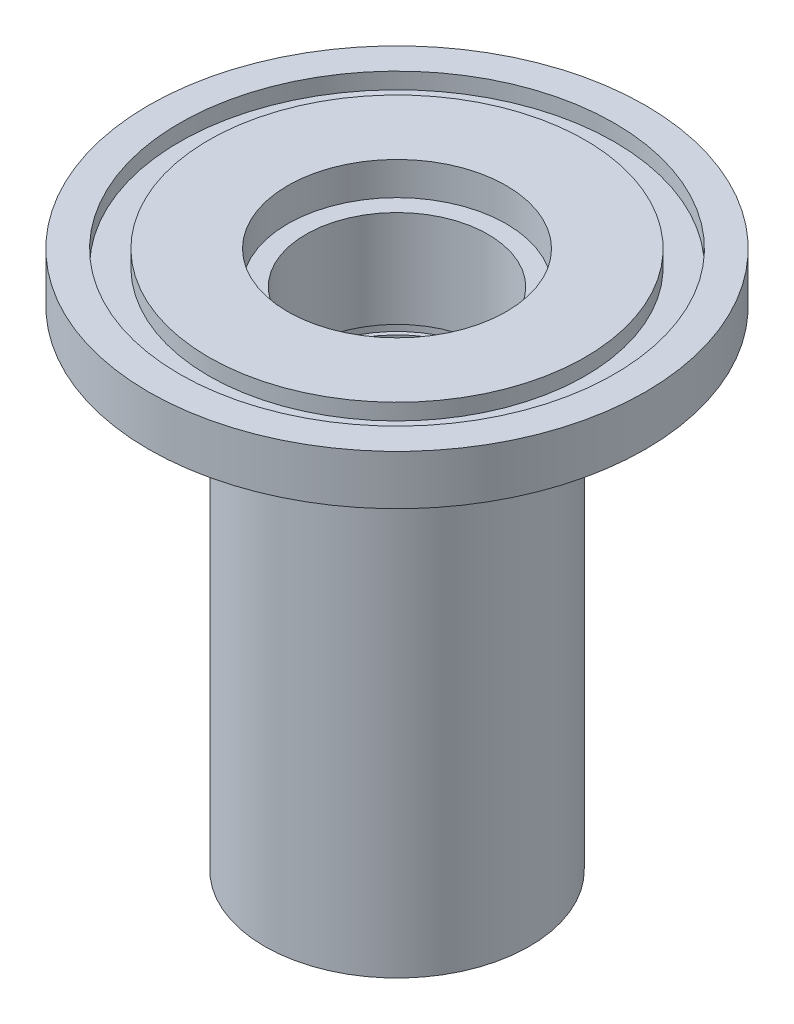
SolidWorks part; units mm, degrees
ref_plane "Front Plane" through (0, 0, 0) normal (0, 0, 1) x (1, 0, 0)
ref_plane "Top Plane" through (0, 0, 0) normal (0, 1, 0) x (1, 0, 0)
ref_plane "Right Plane" through (0, 0, 0) normal (1, 0, 0) x (0, 0, -1)
sketch "Sketch1" plane through (0, 0, 0) normal (0, 0, 1) x (1, 0, 0)
  line L0 (0, 0) -> (0, -122.9972) construction
  line L1 (30, 0) -> (26.2636, 0)
  line L2 (13.2, 0) -> (13.2, -4)
  line L3 (13.2, -4) -> (11, -4)
  line L4 (11, -4) -> (11, -15.7)
  line L9 (11, -65) -> (16, -65)
  line L10 (16, -65) -> (16, -6)
  line L11 (16, -6) -> (30, -6)
  line L12 (30, -6) -> (30, 0)
  line L13 (11, -16.8) -> (11, -31.2)
  line L14 (11, -15.7) -> (11.5, -15.7)
  line L16 (11, -16.8) -> (11.5, -16.8)
  line L17 (11.5, -15.7) -> (11.5, -16.8)
  line L18 (11, -31.2) -> (11.5, -31.2)
  line L20 (11, -32.3) -> (11.5, -32.3)
  line L21 (11.5, -31.2) -> (11.5, -32.3)
  line L22 (11, -32.3) -> (11, -65)
  line L23 (22.733, 0) -> (22.733, -1.9558)
  line L24 (22.733, -1.9558) -> (26.2636, -1.9558)
  line L25 (26.2636, -1.9558) -> (26.2636, 0)
  line L26 (22.733, 0) -> (13.2, 0)
  point P21 (22.9936, 0)
  dimension "D1" = 22
  dimension "D2" = 26.4
  dimension "D3" = 4
  dimension "D4" = 15.7
  dimension "D5" = 1.1
  dimension "D6" = 23
  dimension "D7" = 32.3
  dimension "D8" = 65
  dimension "D9" = 6
  dimension "D10" = 32
  dimension "D11" = 60
  dimension "D12" = 52.5272
  dimension "D13" = 1.9558
  dimension "D14" = 3.5306
revolve "Revolve1" add sketch "Sketch1" angle 360 about L0
